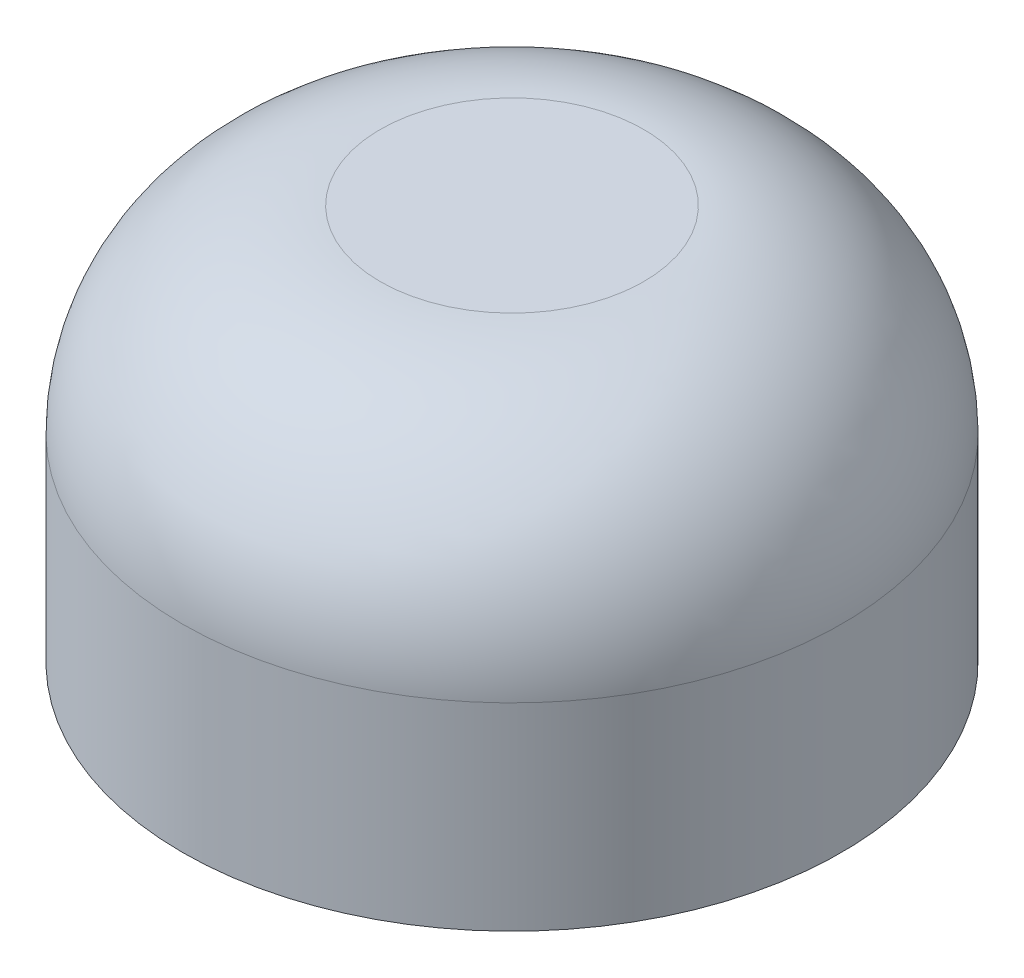
SolidWorks part; units mm, degrees
material "ABS"
ref_plane "Front Plane" through (0, 0, 0) normal (0, 0, 1) x (1, 0, 0)
ref_plane "Top Plane" through (0, 0, 0) normal (0, 1, 0) x (1, 0, 0)
ref_plane "Right Plane" through (0, 0, 0) normal (1, 0, 0) x (0, 0, -1)
sketch "Sketch1" plane through (0, 0, 0) normal (0, 1, 0) x (1, 0, 0)
  circle A0 centre (0, 0) radius 10
  dimension "D1" = 20
extrude "Boss-Extrude1" add sketch "Sketch1" along normal blind 12
fillet "Fillet1" radius 6 1 edges at (0, 12, 10)
